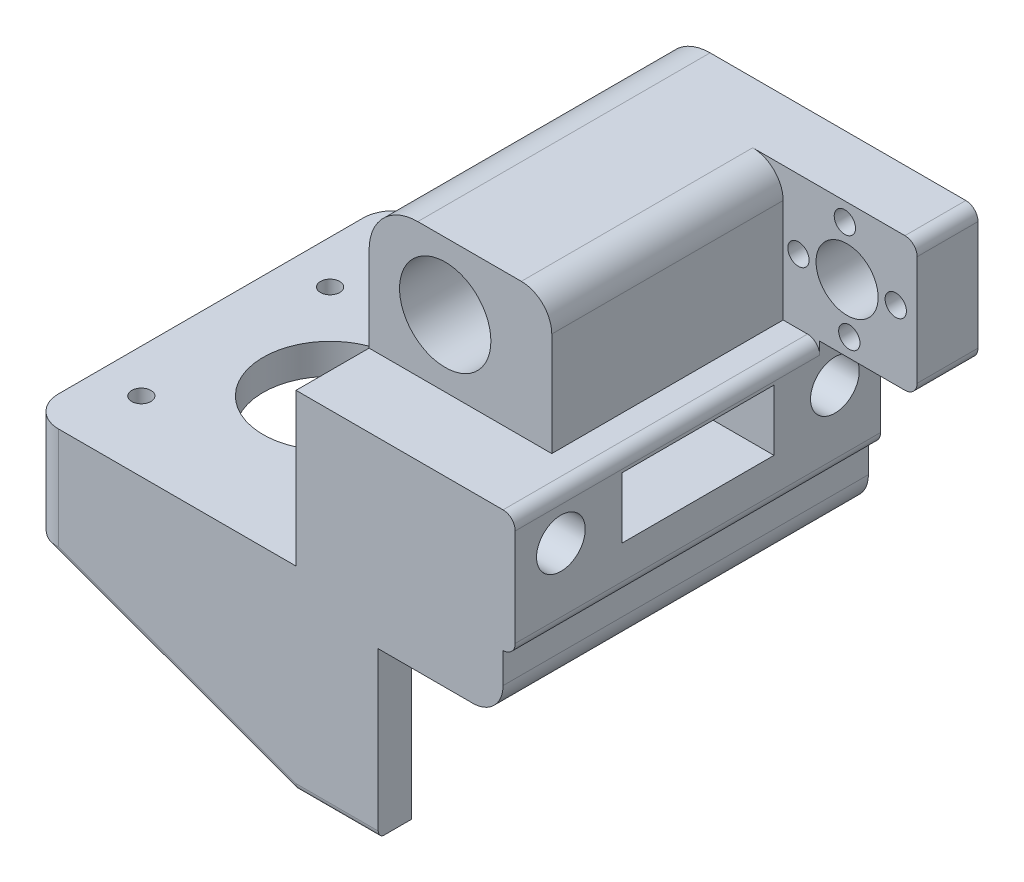
SolidWorks part; units mm, degrees
ref_plane "前视基准面" through (0, 0, 0) normal (0, 0, 1) x (1, 0, 0)
ref_plane "上视基准面" through (0, 0, 0) normal (0, 1, 0) x (1, 0, 0)
ref_plane "右视基准面" through (0, 0, 0) normal (1, 0, 0) x (0, 0, -1)
sketch "草图1" plane through (0, 0, 0) normal (0, 1, 0) x (1, 0, 0)
  line L1 (-40, 30) -> (40, 30)
  line L2 (-40, 30) -> (-40, -30)
  line L3 (-40, -30) -> (40, -30)
  line L4 (40, 30) -> (40, -30)
  line L5 (0, -30) -> (0, 30) construction
  line L6 (-40, 0) -> (40, 0) construction
  point P0 (0, 0)
  dimension "D1" = 80
  dimension "D2" = 60
extrude "凸台-拉伸1" add sketch "草图1" along normal blind 5
sketch "草图2" plane through (0, 5, 0) normal (0, 1, 0) x (1, 0, 0)
  line L0 (-40, 0) -> (40, 0) construction
  line L1 (-40, 30) -> (-40, -30) construction
  line L2 (40, -30) -> (40, 30) construction
  line L4 (-34, 15.5) -> (-3, 15.5) construction
  line L5 (-34, 15.5) -> (-34, -15.5) construction
  line L6 (-34, -15.5) -> (-3, -15.5) construction
  line L7 (-3, 15.5) -> (-3, -15.5) construction
  line L8 (-18.5, -15.5) -> (-18.5, 15.5) construction
  line L9 (-34, 0) -> (-3, 0) construction
  circle A0 centre (-3, 15.5) radius 1.75
  circle A1 centre (-3, -15.5) radius 1.75
  circle A2 centre (-34, -15.5) radius 1.75
  circle A3 centre (-34, 15.5) radius 1.75
  circle A4 centre (-18.5, 0) radius 11
  point P6 (-18.5, 0)
  dimension "D3" = 3.5
  dimension "D4" = 22
  dimension "D1" = 31
  dimension "D2" = 6
extrude "切除-拉伸1" cut sketch "草图2" against normal through all
sketch "草图3" plane through (0, 5, 0) normal (0, 1, 0) x (1, 0, 0)
  line L0 (4, 30) -> (4, -30)
  line L1 (40, 30) -> (-40, 30) construction
  line L2 (-40, -30) -> (40, -30) construction
  line L3 (4, -30) -> (40, -30)
  line L4 (40, -30) -> (40, 30)
  line L5 (40, 30) -> (4, 30)
  circle A0 centre (-3, 15.5) radius 1.75 construction
  dimension "D1" = 7
extrude "凸台-拉伸2" add sketch "草图3" along normal blind 15
sketch "草图4" plane through (4, 0, 0) normal (-1, 0, 0) x (0, 0, 1)
  line L0 (-30, 20) -> (-30, 5) construction
  line L1 (-30, 12.5) -> (30, 12.5) construction
  line L2 (30, 20) -> (30, 5) construction
  line L4 (-12.5, 17.5) -> (12.5, 17.5)
  line L5 (-12.5, 17.5) -> (-12.5, 7.5)
  line L6 (-12.5, 7.5) -> (12.5, 7.5)
  line L7 (12.5, 17.5) -> (12.5, 7.5)
  line L8 (0, 7.5) -> (0, 17.5) construction
  line L9 (-12.5, 12.5) -> (12.5, 12.5) construction
  circle A0 centre (-22.5, 12.5) radius 4
  circle A1 centre (22.5, 12.5) radius 4
  point P10 (0, 12.5)
  dimension "D1" = 8
  dimension "D2" = 45
  dimension "D3" = 7.5
  dimension "D4" = 25
  dimension "D5" = 10
extrude "切除-拉伸7" cut sketch "草图4" against normal through all
sketch "草图14" plane through (0, 20, 0) normal (0, 1, 0) x (1, 0, 0)
  line L0 (4, 30) -> (4, -18)
  line L1 (4, 30) -> (4, -30) construction
  line L2 (4, -18) -> (34, -18)
  line L3 (34, -18) -> (34, 20)
  line L4 (34, 20) -> (56, 20)
  line L5 (56, 20) -> (56, 30)
  line L6 (56, 30) -> (4, 30)
  dimension "D1" = 30
  dimension "D2" = 22
  dimension "D3" = 10
  dimension "D4" = 48
extrude "凸台-拉伸6" add sketch "草图14" along normal blind 22
sketch "草图15" plane through (0, 0, 18) normal (0, 0, 1) x (1, 0, 0)
  line L0 (4, 31) -> (29, 31) construction
  line L1 (4, 42) -> (4, 20) construction
  circle A0 centre (16.5, 31) radius 7.5
  dimension "D1" = 15
  dimension "D2" = 12.5
extrude "切除-拉伸8" cut sketch "草图15" against normal through all
sketch "草图16" plane through (0, 0, -20) normal (0, 0, 1) x (1, 0, 0)
  circle A4 centre (44.5, 31) radius 5.1
  circle A7 centre (16.5, 31) radius 7.5 construction
  dimension "D4" = 10.2
  dimension "D1" = 28
extrude "切除-拉伸9" cut sketch "草图16" against normal through all
fillet "圆角1" radius 8 1 edges at (4, 42, -6)
fillet "圆角2" radius 5 1 edges at (34, 42, -1)
fillet "圆角3" radius 2 1 edges at (56, 42, -25)
fillet "圆角4" radius 2 3 edges at (40, 20, 5) (40, 0, 0) (56, 20, -25)
ref_plane "基准面1" through (0, 0, 22) normal (0, 0, 1) x (1, 0, 0)
sketch "草图18" plane through (0, 0, -30) normal (0, 0, -1) x (-1, 0, 0)
  circle A0 centre (-44.1353, 38.9917) radius 1.75
  circle A1 centre (-36.5083, 30.6353) radius 1.75
  circle A2 centre (-44.8647, 23.0083) radius 1.75
  circle A3 centre (-52.4917, 31.3647) radius 1.75
sketch "草图20" plane through (0, 0, -30) normal (0, 0, -1) x (-1, 0, 0)
  circle A0 centre (-44.1353, 38.9917) radius 1.75
  circle A1 centre (-36.5083, 30.6353) radius 1.75
  circle A2 centre (-44.8647, 23.0083) radius 1.75
  circle A3 centre (-52.4917, 31.3647) radius 1.75
extrude "切除-拉伸11" cut sketch "草图20" against normal through all
ref_plane "基准面2" through (0, 2.5, 0) normal (0, 1, 0) x (1, 0, 0)
sketch "草图23" plane through (0, 0, 0) normal (0, -1, 0) x (1, 0, 0)
  line L4 (-40, -30) -> (38, -30)
  line L5 (38, -30) -> (38, 30)
  line L6 (38, 30) -> (-40, 30)
  line L7 (-40, 30) -> (-40, -30)
  line L8 (-40, -30) -> (38, -30)
  line L9 (38, -30) -> (38, 30)
  line L10 (38, 30) -> (-40, 30)
  line L11 (-40, 30) -> (-40, -30)
  dimension "D1" = 0
extrude "凸台-拉伸8" add sketch "草图23" along normal blind 10
sketch "草图26" plane through (0, 5, 0) normal (0, 1, 0) x (1, 0, 0)
  line L4 (4, -30) -> (4, 30)
  line L5 (4, 30) -> (-40, 30)
  line L6 (-40, 30) -> (-40, -30)
  line L7 (-40, -30) -> (4, -30)
  line L8 (4, -30) -> (4, 30)
  line L9 (4, 30) -> (-40, 30)
  line L10 (-40, 30) -> (-40, -30)
  line L11 (-40, -30) -> (4, -30)
  dimension "D1" = 0
extrude "切除-拉伸13" cut sketch "草图26" against normal blind 10
sketch "草图25" plane through (0, -10, 0) normal (0, -1, 0) x (1, 0, 0)
  line L0 (-1.9022, 18.5053) -> (-32.9022, -12.4947) construction
  line L5 (-1.9022, 18.5053) -> (-32.9022, 18.5053) construction
  line L6 (-1.9022, -12.4947) -> (-32.9022, 18.5053) construction
  line L12 (-32.9022, -12.4947) -> (-32.9022, 18.5053) construction
  line L13 (-1.9022, -12.4947) -> (-1.9022, 18.5053) construction
  line L14 (-1.9022, -12.4947) -> (-32.9022, -12.4947) construction
  circle A5 centre (-32.9022, -12.4947) radius 1.5818
  circle A6 centre (-1.9022, 18.5053) radius 1.5818
  circle A7 centre (-32.9022, 18.5053) radius 1.5818
  circle A9 centre (-1.9022, -12.4947) radius 1.5818
  circle A10 centre (-17.4022, 3.0053) radius 11
  point P26 (-16.1299, 27.4513)
  dimension "D1" = 22
ref_plane "基准面3" through (0, 0, 23) normal (0, 0, 1) x (1, 0, 0)
sketch "草图29" plane through (0, 0, 23) normal (0, 0, 1) x (1, 0, 0)
  line L1 (-40, -5) -> (-40, -21)
  line L2 (-40, -21) -> (4, -37)
  line L3 (4, -37) -> (4, -5)
  line L4 (4, -5) -> (-40, -5)
  dimension "D1" = 16
  dimension "D2" = 32
extrude "凸台-拉伸9" add sketch "草图29" along normal blind 5
fillet "圆角5" radius 5 3 edges at (38, -10, 0) (-40, -7.5, 30) (-40, -7.5, -30)
extrude "切除-拉伸14" cut sketch "草图25" against normal through all
sketch "草图30" plane through (0, 0, 23) normal (0, 0, -1) x (-1, 0, 0)
  line L1 (-4, -10) -> (39, -10) construction
  line L2 (-4, -37) -> (-4, -10) construction
  line L3 (39, -21.3636) -> (-4, -37) construction
  line L5 (-4, -10) -> (40, -10)
  line L6 (-4, -37) -> (-4, -10)
  line L7 (40, -21) -> (-4, -37)
  line L8 (40, -10) -> (40, -21) construction
  line L10 (40, -21) -> (40, -10)
extrude "切除-拉伸15" cut sketch "草图30" against normal blind 1.5
sketch "草图31" plane through (0, 0, 28) normal (0, 0, 1) x (1, 0, 0)
  line L0 (-39.7016, -21.1085) -> (-39.7016, -10)
  line L4 (4, -10) -> (-39, -10)
  line L5 (-39, -10) -> (-39, -21.3636)
  line L6 (-39, -21.3636) -> (4, -37)
  line L7 (4, -37) -> (4, -10)
  line L8 (4, -10) -> (-39.7016, -10)
  line L10 (-39.7016, -21.1085) -> (4, -37)
  line L11 (4, -37) -> (4, -10)
  dimension "D1" = 0
extrude "凸台-拉伸10" add sketch "草图31" along normal up to surface (2 mm away) up to face at (16.6864, 2.3964, 30)
fillet "圆角6" radius 1 4 edges at (-40, -15.5, 24.5) (-17.8508, -29.0543, 30) (-39.7016, -15.5543, 28) (-39.7016, -15.5543, 30)
sketch "草图32" plane through (0, -10, 0) normal (0, 1, 0) x (1, 0, 0)
  line L2 (-39.7016, -28.9544) -> (-39.7016, -29)
  line L3 (-38.7016, -30) -> (-35, -30)
  line L4 (-39.7016, -28.9544) -> (-39.7016, -29)
  line L5 (-38.7016, -30) -> (-35, -30)
  arc A3 (-39, -28) -> (-35, -30) centre (-35, -25) ccw
  arc A4 (-39, -28) -> (-39.7016, -28.9544) centre (-38.7016, -28.9544) ccw
  arc A5 (-39.7016, -29) -> (-38.7016, -30) centre (-38.7016, -29) ccw
  arc A6 (-39, -28) -> (-35, -30) centre (-35, -25) ccw
  arc A7 (-39, -28) -> (-39.7016, -28.9544) centre (-38.7016, -28.9544) ccw
  arc A8 (-39.7016, -29) -> (-38.7016, -30) centre (-38.7016, -29) ccw
  dimension "D1" = 0
extrude "切除-拉伸16" cut sketch "草图32" against normal through all
sketch "草图33" plane through (4, 0, 0) normal (1, 0, 0) x (0, 0, -1)
  line L4 (-30, -10) -> (-30, -35.9359)
  line L5 (-29, -37) -> (-24.5, -37)
  line L6 (-24.5, -37) -> (-24.5, -10)
  line L7 (-24.5, -10) -> (-30, -10)
  line L8 (-30, -10) -> (-30, -35.9359)
  line L9 (-29, -37) -> (-24.5, -37)
  line L10 (-24.5, -37) -> (-24.5, -10)
  line L11 (-24.5, -10) -> (-30, -10)
  ellipse E1 centre (-29, -35.9359) end of major axis (-29, -34.8719) minor radius 1 (-30, -35.9359) -> (-29, -37) ccw
  ellipse E2 centre (-29, -35.9359) end of major axis (-29, -34.8719) minor radius 1 (-30, -35.9359) -> (-29, -37) ccw
  dimension "D1" = 0
extrude "凸台-拉伸11" add sketch "草图33" along normal blind 13.5
